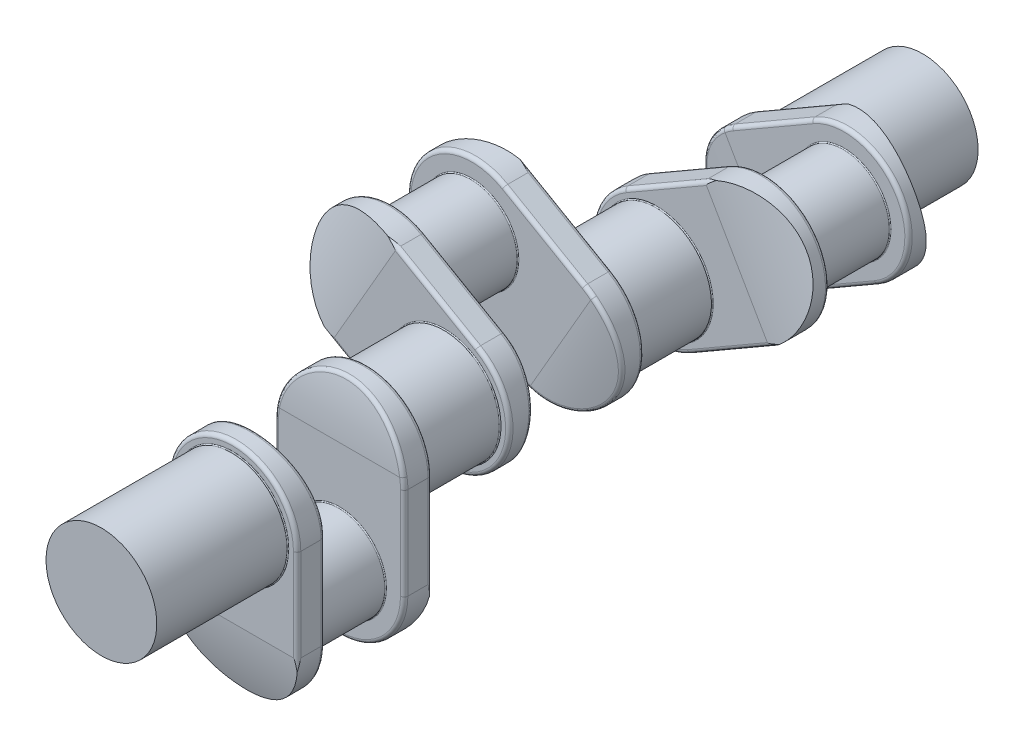
SolidWorks part; units mm, degrees
ref_plane "Front Plane" through (0, 0, 0) normal (0, 0, 1) x (1, 0, 0)
ref_plane "Top Plane" through (0, 0, 0) normal (0, 1, 0) x (1, 0, 0)
ref_plane "Right Plane" through (0, 0, 0) normal (1, 0, 0) x (0, 0, -1)
sketch "Sketch1" plane through (0, 0, 0) normal (0, 0, 1) x (1, 0, 0)
  circle A0 centre (0, 0) radius 31.75
  dimension "D1" = 63.5
extrude "Boss-Extrude1" add sketch "Sketch1" along normal blind 27.31
sketch "Sketch2" plane through (0, 0, 27.31) normal (0, 0, 1) x (1, 0, 0)
  line L0 (-44.45, 63.5) -> (-44.45, 0)
  line L1 (44.45, 63.5) -> (44.45, 0)
  arc A0 (-44.45, 0) -> (44.45, 0) centre (0, 0) ccw
  arc A1 (44.45, 63.5) -> (-44.45, 63.5) centre (0, 63.5) ccw
  circle A2 centre (0, 0) radius 31.75 construction
  dimension "D1" = 12.7
  dimension "D2" = 88.9
  dimension "D3" = 63.5
extrude "Boss-Extrude2" add sketch "Sketch2" along normal blind 19
sketch "Sketch3" plane through (0, 0, 46.31) normal (0, 0, 1) x (1, 0, 0)
  circle A0 centre (0, 63.5) radius 38.1
  dimension "D1" = 76.2
extrude "Boss-Extrude3" add sketch "Sketch3" along normal blind 26.67
sketch "Sketch5" plane through (0, 0, 0) normal (1, 0, 0) x (0, 0, -1)
  line L0 (-46.31, -44.45) -> (-27.31, -44.45) construction
  line L1 (-36.81, -44.45) -> (-59.5213, -44.45)
  line L2 (-59.5213, -44.45) -> (-59.5213, 0)
  line L3 (-59.5213, 0) -> (-46.31, 0)
  line L4 (-27.31, 107.95) -> (-46.31, 107.95) construction
  line L5 (-27.31, 63.5) -> (-27.31, 107.95) construction
  line L6 (-32.31, 107.95) -> (-15.8159, 107.95)
  line L7 (-15.8159, 107.95) -> (-15.8159, 63.5)
  line L8 (-15.8159, 63.5) -> (-27.31, 63.5)
  arc A0 (-46.31, 0) -> (-36.81, -44.45) centre (122.2064, 12.7757) ccw
  arc A1 (-27.31, 63.5) -> (-32.31, 107.95) centre (-196.2738, 67.0002) ccw
  dimension "D1" = 169
  dimension "D2" = 5
  dimension "D3" = 169
extrude "Cut-Extrude1" cut sketch "Sketch5" against normal through all both and the other way through all
fillet "Fillet1" radius 0.64 2 edges at (31.75, 0, 27.31) (38.1, 63.5, 46.31)
fillet "Fillet2" radius 2.54 9 edges at (44.45, 31.75, 46.31) (-44.45, 31.75, 46.31) (-44.45, 31.75, 27.31) (0, -44.45, 27.31) (0, 107.95, 46.31) (3.1078, 107.8412, 32.2829) (44.45, 31.75, 27.31) (-44.3111, 67.0111, 27.31) (44.3111, 67.0111, 27.31)
mirror "Mirror1" about plane through (0, 0, 0) normal (0, 0, 1) of bodies 104
pattern_linear "LPattern1" count 3 spacing 145.96 along (0, 0, -1) of bodies 105
ref_axis "Axis1" through (0, 63.5, 165.2159) along (0, 0, -1)
move or copy body "Body-Move/Copy2" bodies to move or copy 106 copy no rotation origin (0, 63.5, 0) rotation axis (0, 0, -1) rotation angle 120
move or copy body "Body-Move/Copy3" bodies to move or copy 107 copy no rotation origin (0, 63.5, 0) rotation axis (0, 0, 1) rotation angle 120
combine bodies "Combine1" operation type add bodies to combine 105 109 110
sketch "Sketch6" plane through (0, 0, 72.98) normal (0, 0, 1) x (1, 0, 0)
  circle A1 centre (0, 63.5) radius 38.1
  circle A2 centre (0, 63.5) radius 38.1
  dimension "D1" = 0
extrude "Boss-Extrude4" add sketch "Sketch6" along normal blind 63.5
sketch "Sketch7" plane through (0, 0, -364.9) normal (0, 0, -1) x (-1, 0, 0)
  circle A1 centre (0, 63.5) radius 38.1
  circle A2 centre (0, 63.5) radius 38.1
  dimension "D1" = 0
extrude "Boss-Extrude5" add sketch "Sketch7" along normal blind 63.5
